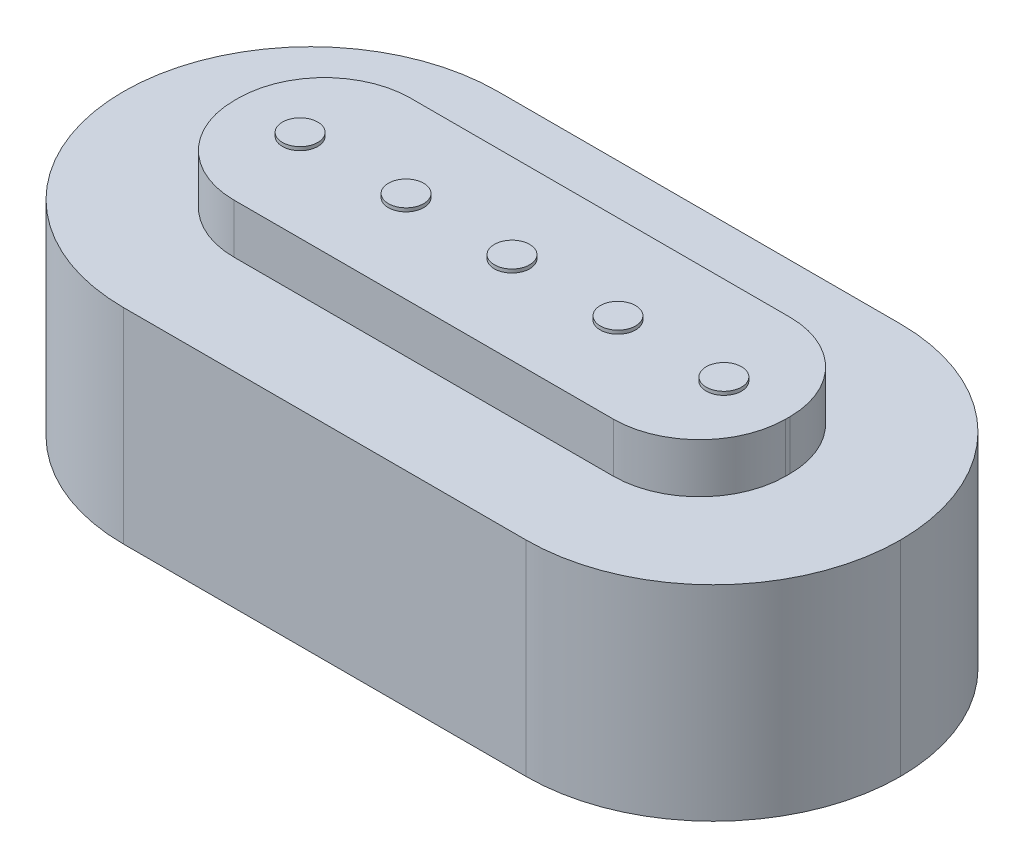
SolidWorks part; units mm, degrees
ref_plane "Front Plane" through (0, 0, 0) normal (0, 0, 1) x (1, 0, 0)
ref_plane "Top Plane" through (0, 0, 0) normal (0, 1, 0) x (1, 0, 0)
ref_plane "Right Plane" through (0, 0, 0) normal (1, 0, 0) x (0, 0, -1)
sketch "Sketch1" plane through (0, 0, 0) normal (0, 1, 0) x (1, 0, 0)
  line L1 (-3.9032, 1.5196) -> (7.0968, 1.5196)
  line L2 (-3.9032, 1.5196) -> (-3.9032, -3.7804)
  line L3 (-3.9032, -3.7804) -> (7.0968, -3.7804)
  line L4 (7.0968, 1.5196) -> (7.0968, -3.7804)
  dimension "D1" = 11
  dimension "D2" = 5.3
extrude "Boss-Extrude1" add sketch "Sketch1" along normal blind 2.9
sketch "Sketch2" plane through (0, 2.9, 0) normal (0, 1, 0) x (1, 0, 0)
  line L0 (1.5968, 1.5196) -> (1.5968, -3.7804) construction
  line L1 (-2.3082, 0.1196) -> (5.5018, 0.1196)
  line L2 (-2.3082, 0.1196) -> (-2.3082, -2.3804)
  line L3 (-2.3082, -2.3804) -> (5.5018, -2.3804)
  line L4 (5.5018, 0.1196) -> (5.5018, -2.3804)
  line L5 (7.0968, 1.5196) -> (-3.9032, 1.5196) construction
  line L6 (-3.9032, -3.7804) -> (7.0968, -3.7804) construction
  line L7 (-3.9032, -1.1304) -> (7.0968, -1.1304) construction
  line L8 (-3.9032, 1.5196) -> (-3.9032, -3.7804) construction
  line L9 (7.0968, -3.7804) -> (7.0968, 1.5196) construction
  point P16 (5.5018, -1.1304)
  point P17 (1.5968, 0.1196)
  dimension "D1" = 7.81
  dimension "D2" = 2.5
extrude "Boss-Extrude2" add sketch "Sketch2" along normal blind 0.7
sketch "Sketch3" plane through (0, 0, 0) normal (0, -1, 0) x (1, 0, 0)
  line L0 (-3.9032, 1.1304) -> (7.0968, 1.1304) construction
  line L1 (-3.9032, -1.5196) -> (-3.9032, 3.7804) construction
  line L2 (7.0968, 3.7804) -> (7.0968, -1.5196) construction
  line L3 (1.5968, 3.7804) -> (1.5968, -1.5196) construction
  line L4 (-3.9032, 3.7804) -> (7.0968, 3.7804) construction
  line L5 (7.0968, -1.5196) -> (-3.9032, -1.5196) construction
  circle A0 centre (1.5968, 1.1304) radius 0.25
  circle A1 centre (3.0968, 1.1304) radius 0.25
  circle A2 centre (4.5968, 1.1304) radius 0.25
  circle A3 centre (0.0968, 1.1304) radius 0.25
  circle A4 centre (-1.4032, 1.1304) radius 0.25
  point P22 (0, 0)
  point P23 (0, 0)
  point P24 (0, 0)
  point P25 (0, 0)
  point P26 (0, 0)
  point P27 (0, 0)
  dimension "D1" = 0.5
  dimension "D2" = 1.5
  dimension "D3" = 3
  dimension "D4" = 1.5
  dimension "D5" = 3
extrude "Boss-Extrude3" add sketch "Sketch3" along normal blind 1.6 and the other way offset from surface (3.65 mm away) 0.05 other way up to face at (1.5968, 3.6, 1.1304)
chamfer "Chamfer1" distance 0.08 angle 45 5 edges at (4.5968, -1.6, 0.8804) (-1.4032, -1.6, 0.8804) (0.0968, -1.6, 0.8804) (1.5968, -1.6, 0.8804) (3.0968, -1.6, 0.8804)
fillet "Fillet1" radius 2.65 4 edges at (-3.9032, 1.45, -1.5196) (-3.9032, 1.45, 3.7804) (7.0968, 1.45, 3.7804) (7.0968, 1.45, -1.5196)
fillet "Fillet2" radius 1.22 4 edges at (-2.3082, 3.25, 2.3804) (-2.3082, 3.25, -0.1196) (5.5018, 3.25, -0.1196) (5.5018, 3.25, 2.3804)
